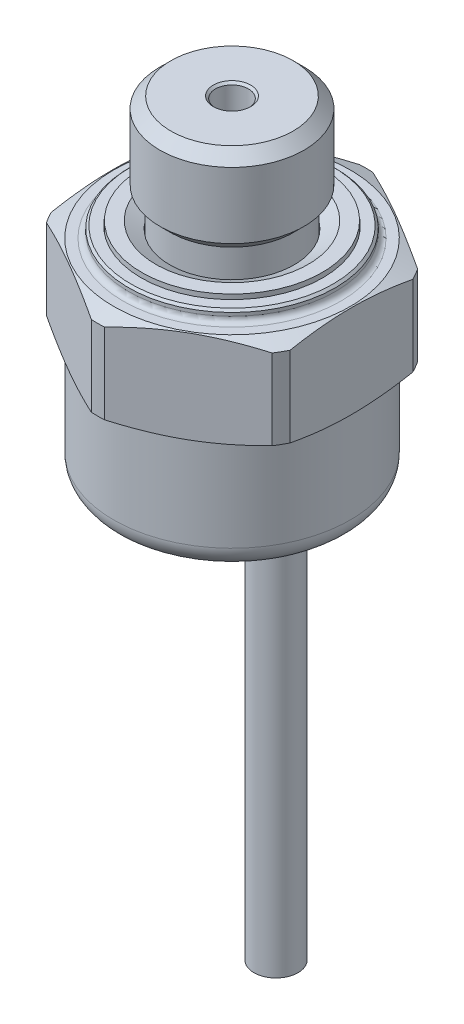
SolidWorks part; units mm, degrees
ref_plane "Front Plane" through (0, 0, 0) normal (0, 0, 1) x (1, 0, 0)
ref_plane "Top Plane" through (0, 0, 0) normal (0, 1, 0) x (1, 0, 0)
ref_plane "Right Plane" through (0, 0, 0) normal (1, 0, 0) x (0, 0, -1)
sketch "Sketch1" plane through (0, 0, 0) normal (0, 0, 1) x (1, 0, 0)
  line L0 (0, 0) -> (0, -31) construction
  line L2 (10.75, -30) -> (10.75, -19.7)
  line L3 (10.75, -19.7) -> (12.2, -19.0994)
  line L4 (12.2, -19.0994) -> (12.2, -11.8006)
  line L6 (9.4, -11.2) -> (9.4, -10.2)
  line L7 (9.4, -10.2) -> (8.25, -10.2)
  line L8 (8.25, -10.2) -> (8.25, -11.2)
  line L9 (8.25, -11.2) -> (5.6, -11.2)
  line L10 (5.6, -11.2) -> (5.6, -8)
  line L11 (5.6, -8) -> (6.55, -8)
  line L12 (6.55, -8) -> (6.55, 0)
  line L13 (6.55, 0) -> (0, 0) construction
  line L14 (9.4, -11.2) -> (10.75, -11.2)
  line L15 (10.75, -11.2) -> (12.2, -11.8006)
  line L16 (12.2, -15.45) -> (9.4, -15.45) construction
  line L17 (0, -31) -> (-6.55, -31) construction
  line L18 (10.75, -30) -> (8.75, -30)
  line L19 (8.2, -10.2) -> (8.2, -11.15) construction
  line L20 (5.65, -9.8) -> (8.2, -9.8) construction
  line L21 (5.65, -9.8) -> (5.65, -11.15) construction
  line L22 (5.65, -11.15) -> (8.2, -11.15)
  line L23 (8.2, -9.8) -> (8.2, -11.15)
  line L24 (8.2, -11.15) -> (5.65, -11.15) construction
  line L25 (5.65, -11.15) -> (5.65, -8) construction
  line L26 (8.2, -9.8) -> (6.925, -9.8)
  line L27 (6.925, -9.8) -> (5.65, -10.475)
  line L28 (5.65, -10.475) -> (5.65, -11.15)
  line L29 (6.55, 0) -> (1.5, 0)
  line L30 (1.5, 0) -> (1.5, -10)
  line L31 (1.5, -10) -> (0, -10)
  line L32 (0, -10) -> (0, -31)
  arc A1 (8.75, -30) -> (0, -31) centre (0, 7.7812) cw
  point P16 (-10.75, -30)
  point P19 (-12.2, -11.8006)
  point P20 (-9.4, -10.2)
  point P21 (-8.25, -10.2)
  point P22 (-5.6, -8)
  point P23 (-6.55, 0)
  point P36 (-1.5, -10)
  dimension "D7" = 30
  dimension "D8" = 1
  dimension "D1" = 21.5
  dimension "D2" = 24.4
  dimension "D3" = 18.8
  dimension "D4" = 16.5
  dimension "D5" = 11.2
  dimension "D6" = 13.1
  dimension "D9" = 2
  dimension "D10" = 45
  dimension "D11" = 11.2
  dimension "D12" = 8.5
  dimension "D13" = 1
  dimension "D14" = 8
  dimension "D15" = 0.05
  dimension "D16" = 0.4
  dimension "D17" = 3
  dimension "D18" = 10
revolve "Revolve1" add sketch "Sketch1" angle 360 about L0
sketch "Sketch2" plane through (0, 0, 0) normal (0, 1, 0) x (1, 0, 0)
  line L1 (0, 12.5285) -> (-10.85, 6.2643)
  line L2 (-10.85, 6.2643) -> (-10.85, -6.2643)
  line L3 (-10.85, -6.2643) -> (0, -12.5285)
  line L4 (0, -12.5285) -> (10.85, -6.2643)
  line L5 (10.85, -6.2643) -> (10.85, 6.2643)
  line L6 (10.85, 6.2643) -> (0, 12.5285)
  circle A0 centre (0, 0) radius 10.85 construction
  circle A1 centre (0, 0) radius 12.2 construction
  circle A2 centre (0, 0) radius 12.2
  dimension "D1" = 21.7
extrude "Cut-Extrude2" cut sketch "Sketch2" against normal through all contours L1 A2 | L6 A2 | L5 A2 | L4 A2 | L3 A2 | L2 A2
fillet "Fillet1" radius 2 1 edges at (-10.75, -30, 0)
chamfer "Chamfer1" distance 1 angle 45 2 edges at (-6.55, -8, 0) (-6.55, 0, 0)
chamfer "Chamfer2" distance 0.2 angle 45 1 edges at (-1.5, -10, 0)
fillet "Fillet2" radius 0.5 1 edges at (-9.4, -11.2, 0)
sketch "Sketch5" plane through (0, 0, 0) normal (0, 1, 0) x (1, 0, 0)
  line L0 (0, 0) -> (0, 4) construction
  circle A0 centre (0, 4) radius 2
  dimension "D1" = 4
  dimension "D2" = 4
extrude "Boss-Extrude1" add sketch "Sketch5" against normal blind 50 from offset 20 separate body
